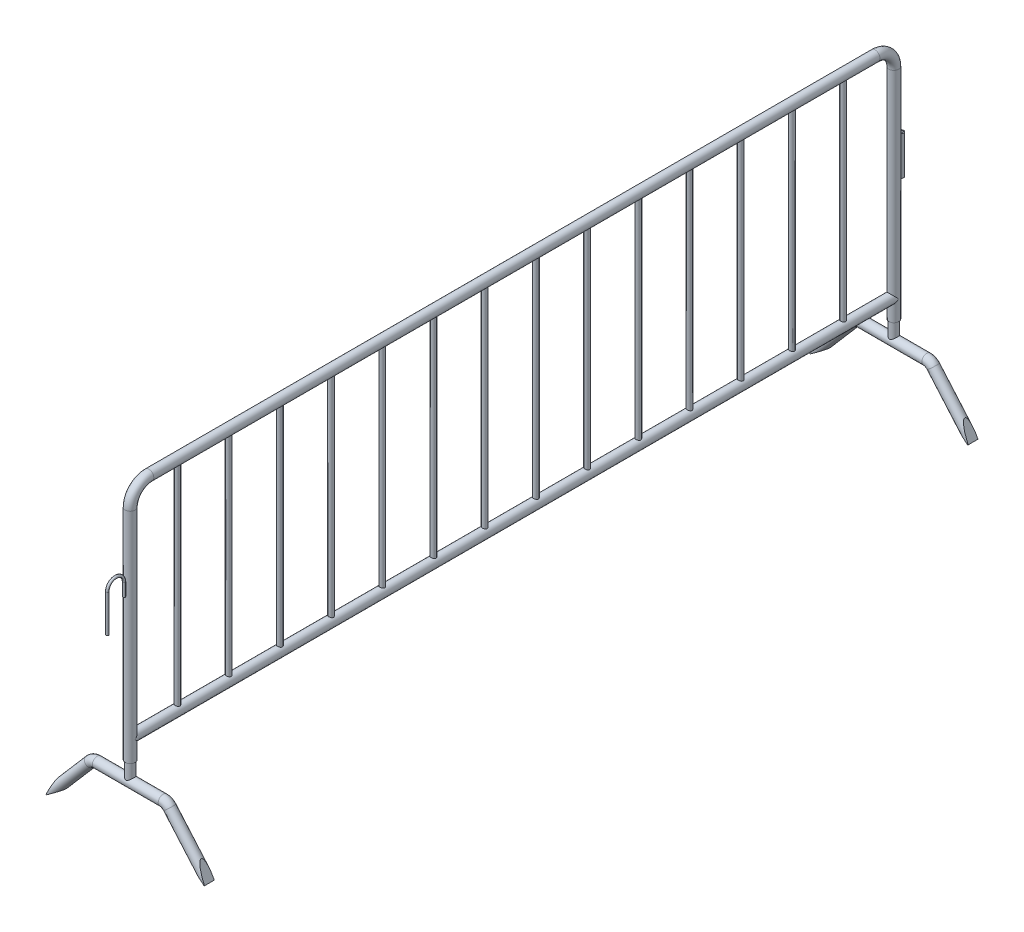
SolidWorks part; units mm, degrees
ref_plane "Front" through (0, 0, 0) normal (0, 0, 1) x (1, 0, 0)
ref_plane "Top" through (0, 0, 0) normal (0, 1, 0) x (1, 0, 0)
ref_plane "Right" through (0, 0, 0) normal (1, 0, 0) x (0, 0, -1)
sketch "Sketch1" plane through (0, 0, 0) normal (1, 0, 0) x (0, 0, -1)
  line L0 (-1246.9812, 0) -> (1246.9812, 0) construction
  line L1 (-1246.9812, 0) -> (-1246.9813, -998.5375) construction
  line L3 (0, -717.55) -> (0, 0) construction
  line L4 (-1246.9813, -717.55) -> (1246.9812, -717.55) construction
  point P4 (0, -717.55)
  point P5 (-1215.2313, -717.55)
  point P9 (-1085.396, -717.55)
  point P10 (-1246.9812, -781.05)
  point P12 (-1246.9812, -395.2875)
  point P13 (1246.9812, -409.575)
  dimension "D1" = 31.75
  dimension "D2" = 280.9875
  dimension "D3" = 2493.9625
  dimension "D4" = 63.5
  dimension "D5" = 129.8353
  dimension "D6" = 998.5375
  dimension "D7" = 603.25
  dimension "D8" = 588.9625
sketch "Sketch2" plane through (0, 0, 0) normal (1, 0, 0) x (0, 0, -1)
  line L0 (-1246.9813, -711.2) -> (-1246.9813, -76.2)
  line L1 (-1170.7812, 0) -> (1170.7812, 0)
  line L2 (1246.9812, -76.2) -> (1246.9812, -711.2)
  line L3 (-1246.9813, -711.2) -> (-1246.9812, -781.05)
  line L4 (1246.9812, -711.2) -> (1246.9812, -781.05)
  arc A0 (1170.7812, 0) -> (1246.9812, -76.2) centre (1170.7812, -76.2) cw
  arc A1 (-1246.9813, -76.2) -> (-1170.7812, 0) centre (-1170.7812, -76.2) cw
  point P9 (1246.9812, 0)
  point P12 (-1246.9812, 0)
  dimension "D1" = 76.2
  dimension "D2" = 76.2
  dimension "D3" = 711.2
ref_plane "Plane1" through (0, -781.05, 0) normal (0, 1, 0) x (1, 0, 0)
sketch "Sketch3" plane through (0, -781.05, 0) normal (0, 1, 0) x (1, 0, 0)
  line L0 (0, -1246.9813) -> (0, -833.8788) construction
  circle A0 centre (0, -1231.1063) radius 15.875
  point P7 (0, -1231.1063)
  dimension "D1" = 31.75
sweep "Sweep1" add profiles "Sketch3" path "Sketch2"
sketch "Sketch4" plane through (0, 0, 0) normal (0, 0, 1) x (1, 0, 0)
  circle A0 centre (0, -717.55) radius 15.875
  dimension "D1" = 31.75
extrude "Boss-Extrude1" add sketch "Sketch4" along normal up to next and the other way up to next
ref_plane "Plane2" through (0, -22.225, 0) normal (0, 1, 0) x (1, 0, 0)
sketch "Sketch6" plane through (0, -22.225, 0) normal (0, 1, 0) x (1, 0, 0)
  line L0 (0, -1246.9812) -> (0, 1246.9812) construction
  circle A0 centre (0, -1078.7062) radius 7.9375
  circle A1 centre (0, -913.6063) radius 7.9375
  point P8 (0, -1070.7687)
  point P9 (0, -921.5438)
  point P10 (0, -1086.6437)
  point P11 (0, -905.6688)
  dimension "D1" = 15.875
  dimension "D2" = 152.4
  dimension "D3" = 149.225
  dimension "D4" = 165.1
extrude "Boss-Extrude2" add sketch "Sketch6" against normal up to surface (679.45 mm away) separate body up to face at (0, -717.55, -1215.2312)
pattern_linear "LPattern1" count 13 spacing 165.1 along (0, 0, -1) of "Boss-Extrude2"
ref_plane "Plane3" through (0, 0, 1231.1063) normal (0, 0, 1) x (1, 0, 0)
sketch "Sketch7" plane through (0, 0, 1231.1063) normal (0, 0, 1) x (1, 0, 0)
  line L0 (-255.5875, -781.05) -> (255.5875, -781.05) construction
  line L1 (-255.5875, -781.05) -> (-255.5875, -998.5375) construction
  line L2 (-255.5875, -998.5375) -> (0, -998.5375) construction
  line L3 (0, 0) -> (0, -998.5375) construction
  dimension "D1" = 511.175
sketch "Sketch8" plane through (0, -781.05, 0) normal (0, -1, 0) x (1, 0, 0)
  circle A0 centre (0, 1231.1063) radius 13.3858
  dimension "D1" = 26.7716
extrude "Boss-Extrude3" add sketch "Sketch8" along normal blind 50.8 separate body
sketch "Sketch9" plane through (0, 0, 0) normal (1, 0, 0) x (0, 0, -1)
  line L3 (-1244.4921, -831.85) -> (-1217.7204, -831.85) construction
  circle A0 centre (-1231.1063, -840.2854) radius 15.875
  point P6 (-1231.1063, -856.1604)
  dimension "D1" = 31.75
  dimension "D2" = 8.4354
sketch "Sketch10" plane through (0, 0, 1231.1063) normal (0, 0, 1) x (1, 0, 0)
  line L0 (0, -840.2854) -> (-106.1453, -840.2854)
  line L1 (0, 0) -> (0, -998.5375) construction
  line L2 (-127.7937, -850.209) -> (-255.5875, -998.5375)
  line L3 (-127.7937, -998.5375) -> (-127.7937, -781.05) construction
  line L4 (-255.5875, -998.5375) -> (0, -998.5375) construction
  line L5 (-255.5875, -781.05) -> (255.5875, -781.05) construction
  arc A0 (-106.1453, -840.2854) -> (-127.7937, -850.209) centre (-106.1453, -868.8604) ccw
  dimension "D2" = 28.575
sweep "Sweep2" add profiles "Sketch9" path "Sketch10"
sketch "Sketch13" plane through (0, 0, 1231.1063) normal (0, 0, 1) x (1, 0, 0)
  line L0 (-255.5875, -997.4335) -> (-254.3061, -998.5375)
  line L1 (-255.5875, -781.05) -> (-255.5875, -998.5375) construction
  line L2 (-255.5875, -998.5375) -> (0, -998.5375) construction
  line L3 (-254.3061, -998.5375) -> (-204.7875, -963.896)
  line L4 (-204.7875, -963.896) -> (-204.7875, -1023.9375)
  line L5 (-255.5875, -997.4335) -> (-228.8833, -943.2209)
  line L6 (-228.8833, -943.2209) -> (-280.9875, -943.2209)
  line L7 (-280.9875, -943.2209) -> (-280.9875, -1023.9375)
  line L8 (-280.9875, -1023.9375) -> (-204.7875, -1023.9375)
  line L9 (-267.6144, -988.1756) -> (-243.5606, -1008.8994) construction
  line L10 (-243.5606, -1008.8994) -> (-115.7668, -860.5709) construction
  line L11 (-228.8833, -943.2209) -> (-204.7875, -943.2209) construction
  line L12 (-204.7875, -943.2209) -> (-204.7875, -963.896) construction
  line L15 (-139.8207, -839.8471) -> (-267.6144, -988.1756) construction
  line L16 (-228.8833, -943.2209) -> (-204.7875, -963.896) construction
  dimension "D1" = 1.6913
  dimension "D2" = 25.4
  dimension "D3" = 25.4
  dimension "D4" = 76.2
extrude "Cut-Extrude1" cut sketch "Sketch13" against normal through all both and the other way through all
mirror "Mirror1" about plane through (0, 0, 0) normal (1, 0, 0) of "Cut-Extrude1", "Sweep2"
mirror "Mirror3" about plane through (0, 0, 0) normal (0, 0, 1) of bodies 152
sketch "Sketch14" plane through (0, 0, 0) normal (1, 0, 0) x (0, 0, -1)
  line L0 (-1304.925, -395.2875) -> (-1304.925, -274.2753)
  line L1 (-1250.95, -274.2753) -> (-1250.95, -315.6804)
  line L3 (-1246.9812, 0) -> (-1246.9813, -998.5375) construction
  arc A0 (-1304.925, -274.2753) -> (-1250.95, -274.2753) centre (-1277.9375, -274.2753) cw
  point P9 (-1277.9375, -247.2878)
  dimension "D1" = 53.975
  dimension "D2" = 3.9688
  dimension "D3" = 68.3926
  dimension "D4" = 147.9997
ref_plane "Plane4" through (0, -395.2875, 0) normal (0, 1, 0) x (1, 0, 0)
sketch "Sketch15" plane through (0, -395.2875, 0) normal (0, 1, 0) x (1, 0, 0)
  circle A0 centre (0, -1304.925) radius 3.9687
  dimension "D1" = 7.9375
sweep "Sweep3" add profiles "Sketch15" path "Sketch14"
sketch "Sketch16" plane through (0, -395.2875, 0) normal (0, 1, 0) x (1, 0, 0)
  circle A0 centre (0, 1254.9187) radius 7.9375
  circle A1 centre (0, 1254.9187) radius 5.08
  point P3 (0, 1246.9812)
  dimension "D1" = 10.16
  dimension "D2" = 15.875
extrude "Boss-Extrude4" add sketch "Sketch16" along normal blind 124.7775 separate body
